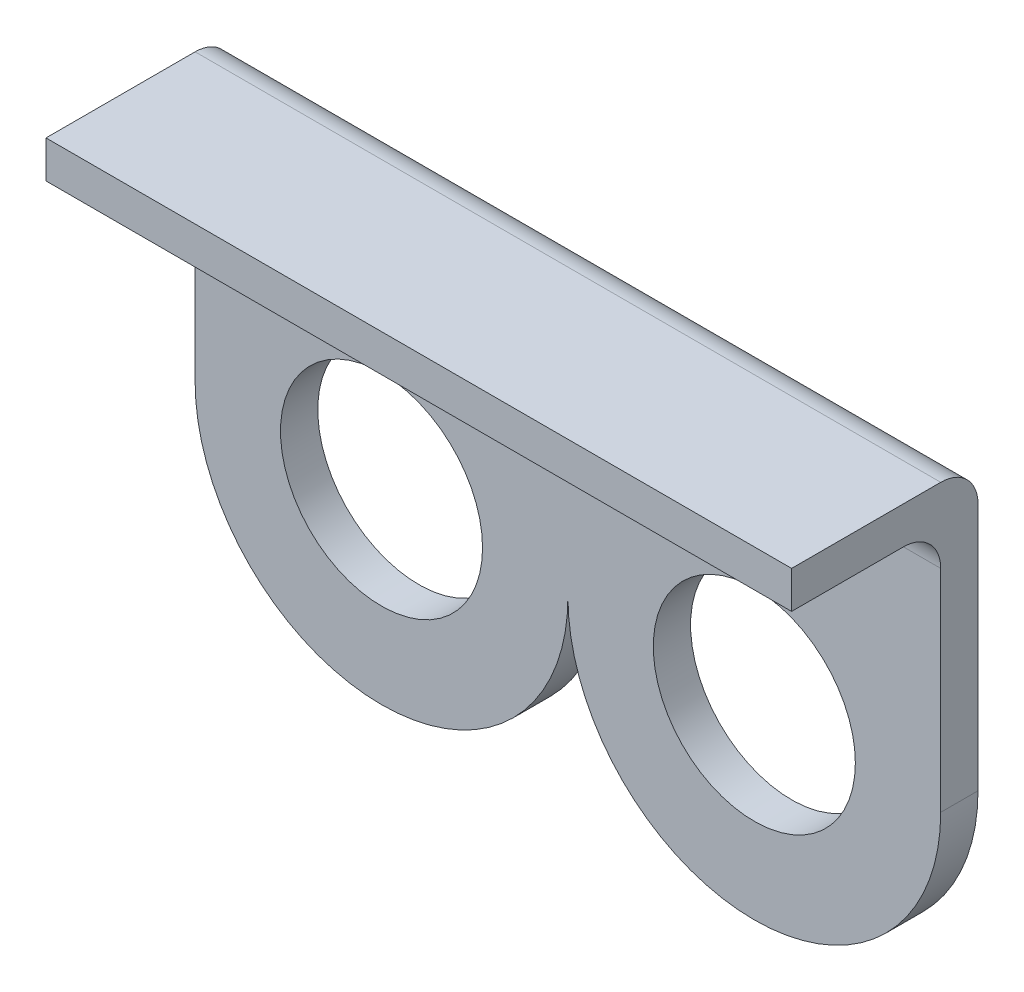
SolidWorks part; units mm, degrees
ref_plane "Front Plane" through (0, 0, 0) normal (0, 0, 1) x (1, 0, 0)
ref_plane "Top Plane" through (0, 0, 0) normal (0, 1, 0) x (1, 0, 0)
ref_plane "Right Plane" through (0, 0, 0) normal (1, 0, 0) x (0, 0, -1)
sketch "Sketch1" plane through (0, 0, 0) normal (0, 0, 1) x (1, 0, 0)
  line L0 (0, -17.5) -> (0, 20.5) construction
  line L1 (-30, 17.5) -> (30, 17.5)
  line L2 (-30, 17.5) -> (-30, -17.5)
  line L3 (-30, -17.5) -> (30, -17.5)
  line L4 (30, 17.5) -> (30, -17.5)
  line L5 (-30, 17.5) -> (30, -17.5) construction
  line L6 (-30, -17.5) -> (30, 17.5) construction
  line L7 (-30, 17.5) -> (30, 17.5)
  line L8 (-30, 17.5) -> (-30, 20.5)
  line L9 (-30, 20.5) -> (30, 20.5)
  line L10 (30, 17.5) -> (30, 20.5)
  circle A0 centre (-15, -2.5) radius 8.13
  arc A1 (-30, -2.5) -> (0, -2.5) centre (-15, -2.5) ccw
  circle A2 centre (15, -2.5) radius 8.13
  arc A3 (30, -2.5) -> (0, -2.5) centre (15, -2.5) cw
  point P0 (0, 0)
  dimension "D4" = 16.26
  dimension "D1" = 3
  dimension "D2" = 60
  dimension "D3" = 35
  dimension "D5" = 15
  dimension "D6" = 15
extrude "Boss-Extrude2" add sketch "Sketch1" along normal blind 15 contours L8 L7 L10 L9
extrude "Boss-Extrude3" add sketch "Sketch1<5>" along normal blind 3 contours A3 L4 L1 L2 A1 A0 A2 region at (0, 2.5283, 0)
sketch "Sketch1<5>" plane through (0, 0, 0) normal (0, 0, 1) x (1, 0, 0) same geometry as "Sketch1"
fillet "Fillet1" radius 3 1 edges at (0, 17.5, 3)
fillet "Fillet2" radius 3 1 edges at (0, 20.5, 0)
